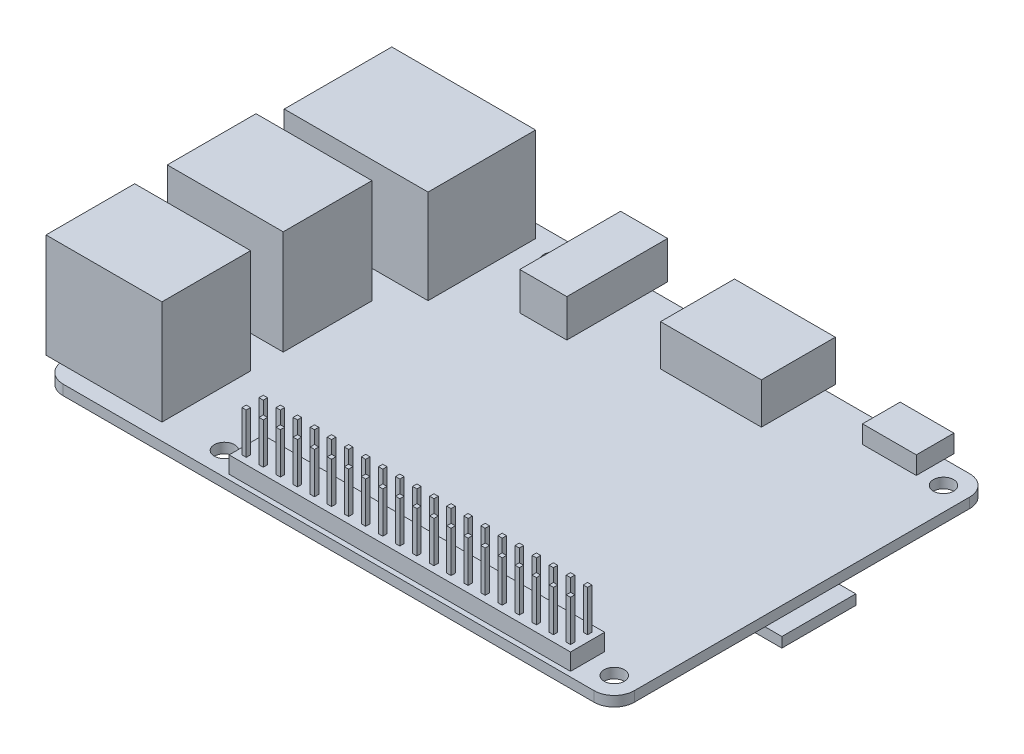
SolidWorks part; units mm, degrees
ref_plane "Front Plane" through (0, 0, 0) normal (0, 0, 1) x (1, 0, 0)
ref_plane "Top Plane" through (0, 0, 0) normal (0, 1, 0) x (1, 0, 0)
ref_plane "Right Plane" through (0, 0, 0) normal (1, 0, 0) x (0, 0, -1)
sketch "Sketch1" plane through (0, 0, 0) normal (0, 1, 0) x (1, 0, 0)
  line L0 (39.05, 24.5) -> (39.05, 27.95) construction
  line L1 (-39.5, -27.95) -> (39.5, -27.95)
  line L2 (-42.5, -24.95) -> (-42.5, 24.95)
  line L3 (-39.5, 27.95) -> (39.5, 27.95)
  line L4 (42.5, -24.95) -> (42.5, 24.95)
  line L5 (-42.5, -27.95) -> (42.5, 27.95) construction
  line L6 (-42.5, 27.95) -> (42.5, -27.95) construction
  line L7 (-18.95, -24.5) -> (39.05, -24.5) construction
  line L8 (-18.95, -24.5) -> (-18.95, 24.5) construction
  line L9 (-18.95, 24.5) -> (39.05, 24.5) construction
  line L10 (39.05, -24.5) -> (39.05, 24.5) construction
  line L11 (39.05, -24.5) -> (39.05, -27.95) construction
  line L12 (39.05, 24.5) -> (42.5, 24.5) construction
  circle A0 centre (-18.95, 24.5) radius 1.5
  circle A1 centre (39.05, 24.5) radius 1.5
  circle A2 centre (39.05, -24.5) radius 1.5
  circle A3 centre (-18.95, -24.5) radius 1.5
  arc A4 (39.5, 27.95) -> (42.5, 24.95) centre (39.5, 24.95) cw
  arc A5 (39.5, -27.95) -> (42.5, -24.95) centre (39.5, -24.95) ccw
  arc A6 (-39.5, -27.95) -> (-42.5, -24.95) centre (-39.5, -24.95) cw
  arc A7 (-42.5, 24.95) -> (-39.5, 27.95) centre (-39.5, 24.95) cw
  point P0 (0, 0)
  point P6 (0, 0)
  dimension "D1" = 3
  dimension "D6" = 3
  dimension "D2" = 85
  dimension "D3" = 55.9
  dimension "D4" = 49
  dimension "D5" = 58
extrude "Boss-Extrude1" add sketch "Sketch1" along normal blind 1.5
sketch "Sketch2" plane through (0, 0, 0) normal (0, -1, 0) x (1, 0, 0)
  line L0 (0, 0) -> (37.25, 0) construction
  line L1 (29.5, -5.5) -> (45, -5.5)
  line L2 (29.5, -5.5) -> (29.5, 5.5)
  line L3 (29.5, 5.5) -> (45, 5.5)
  line L4 (45, -5.5) -> (45, 5.5)
  line L5 (29.5, -5.5) -> (45, 5.5) construction
  line L6 (29.5, 5.5) -> (45, -5.5) construction
  line L7 (42.5, 24.95) -> (42.5, -24.95) construction
  point P0 (37.25, 0)
  dimension "D1" = 11
  dimension "D2" = 2.5
  dimension "D3" = 15.5
extrude "Boss-Extrude2" add sketch "Sketch2" along normal blind 1.5
sketch "Sketch3" plane through (0, 1.5, 0) normal (0, 1, 0) x (1, 0, 0)
  line L0 (39.5, 27.95) -> (-39.5, 27.95) construction
  line L1 (-44.5, 25.95) -> (-23.1, 25.95)
  line L2 (-44.5, 25.95) -> (-44.5, 9.95)
  line L3 (-44.5, 9.95) -> (-23.1, 9.95)
  line L4 (-23.1, 25.95) -> (-23.1, 9.95)
  line L5 (-42.5, 24.95) -> (-42.5, -24.95) construction
  dimension "D1" = 21.4
  dimension "D2" = 16
  dimension "D3" = 2
  dimension "D4" = 2
extrude "Boss-Extrude3" add sketch "Sketch3" along normal blind 14
sketch "Sketch4" plane through (0, 1.5, 0) normal (0, 1, 0) x (1, 0, 0)
  line L0 (-42.5, 9.95) -> (-23.1, 9.95) construction
  line L1 (-44.5, 5.75) -> (-27.25, 5.75)
  line L2 (-44.5, 5.75) -> (-44.5, -7.45)
  line L3 (-44.5, -7.45) -> (-27.25, -7.45)
  line L4 (-27.25, 5.75) -> (-27.25, -7.45)
  line L5 (-44.5, -12.3) -> (-27.25, -12.3)
  line L6 (-44.5, -12.3) -> (-44.5, -25.5)
  line L7 (-44.5, -25.5) -> (-27.25, -25.5)
  line L8 (-27.25, -12.3) -> (-27.25, -25.5)
  line L9 (-44.5, 25.95) -> (-44.5, 9.95) construction
  dimension "D1" = 4.2
  dimension "D2" = 13.2
  dimension "D3" = 4.85
  dimension "D4" = 17.25
extrude "Boss-Extrude4" add sketch "Sketch4" along normal blind 15.5
sketch "Sketch5" plane through (0, 1.5, 0) normal (0, 1, 0) x (1, 0, 0)
  line L0 (39.5, 27.95) -> (-39.5, 27.95) construction
  line L1 (18, 18.45) -> (3, 18.45)
  line L2 (18, 18.45) -> (18, 29.45)
  line L3 (18, 29.45) -> (3, 29.45)
  line L4 (3, 18.45) -> (3, 29.45)
  line L5 (42.5, -24.95) -> (42.5, 24.95) construction
  dimension "D1" = 1.5
  dimension "D2" = 15
  dimension "D3" = 11
  dimension "D4" = 24.5
extrude "Boss-Extrude5" add sketch "Sketch5" along normal blind 6.1 contours L1 L4 L3 L2
sketch "Sketch6" plane through (0, 1.5, 0) normal (0, 1, 0) x (1, 0, 0)
  line L0 (3, 27.95) -> (-39.5, 27.95) construction
  line L1 (-14.7, 15.2) -> (-7.7, 15.2)
  line L2 (-14.7, 15.2) -> (-14.7, 30.2)
  line L3 (-14.7, 30.2) -> (-7.7, 30.2)
  line L4 (-7.7, 15.2) -> (-7.7, 30.2)
  line L5 (-23.1, 9.95) -> (-23.1, 25.95) construction
  dimension "D1" = 7
  dimension "D2" = 15
  dimension "D3" = 2.25
  dimension "D4" = 8.4
extrude "Boss-Extrude6" add sketch "Sketch6" along normal blind 5.6
sketch "Sketch7" plane through (0, 1.5, 0) normal (0, 1, 0) x (1, 0, 0)
  line L0 (39.5, 27.95) -> (18, 27.95) construction
  line L1 (27.75, 23.75) -> (35.75, 23.75)
  line L2 (27.75, 23.75) -> (27.75, 29.35)
  line L3 (27.75, 29.35) -> (35.75, 29.35)
  line L4 (35.75, 23.75) -> (35.75, 29.35)
  line L5 (42.5, -24.95) -> (42.5, 24.95) construction
  dimension "D1" = 8
  dimension "D2" = 5.6
  dimension "D3" = 1.4
  dimension "D4" = 6.75
extrude "Boss-Extrude7" add sketch "Sketch7" along normal blind 2.66 contours L1 L4 L3 L2
sketch "Sketch8" plane through (0, 1.5, 0) normal (0, 1, 0) x (1, 0, 0)
  line L0 (42.5, -24.95) -> (42.5, 24.95) construction
  line L1 (35.27, -27.22) -> (32.73, -27.22)
  line L2 (35.27, -27.22) -> (35.27, -24.68)
  line L3 (35.27, -24.68) -> (32.73, -24.68)
  line L4 (32.73, -27.22) -> (32.73, -24.68)
  line L5 (35.27, -27.22) -> (32.73, -24.68) construction
  line L6 (35.27, -24.68) -> (32.73, -27.22) construction
  line L7 (34.32, -26.27) -> (33.68, -26.27)
  line L8 (34.32, -26.27) -> (34.32, -25.63)
  line L9 (34.32, -25.63) -> (33.68, -25.63)
  line L10 (33.68, -26.27) -> (33.68, -25.63)
  line L11 (34.32, -26.27) -> (33.68, -25.63) construction
  line L12 (34.32, -25.63) -> (33.68, -26.27) construction
  line L13 (-39.5, -27.95) -> (39.5, -27.95) construction
  point P0 (34, -25.95)
  point P5 (34, -25.95)
  dimension "D1" = 8.5
  dimension "D2" = 0.64
  dimension "D3" = 2.54
  dimension "D4" = 2
extrude "Boss-Extrude8" add sketch "Sketch8" along normal blind 2.5 contours L1 L4 L3 L2
extrude "Boss-Extrude9" add sketch "Sketch8<3>" along normal blind 8.6 contours L10 L7 L8 L9 region at (34, 1.5, 25.95)
sketch "Sketch8<3>" plane through (0, 1.5, 0) normal (0, 1, 0) x (1, 0, 0) same geometry as "Sketch8"
pattern_linear "LPattern1" count 20 spacing 2.54 along (-1, 0, 0) count 2 spacing 2.54 along (0, 0, -1) of "Boss-Extrude8", "Boss-Extrude9"
